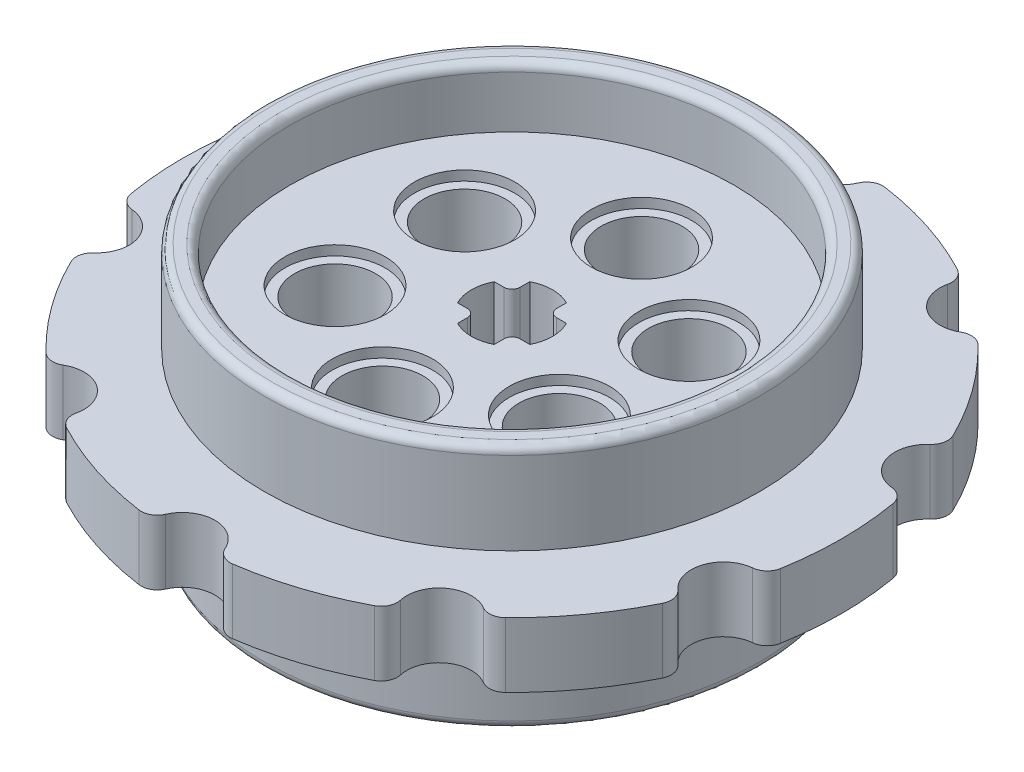
SolidWorks part; units mm, degrees
ref_plane "前视基准面" through (0, 0, 0) normal (0, 0, 1) x (1, 0, 0)
ref_plane "上视基准面" through (0, 0, 0) normal (0, 1, 0) x (1, 0, 0)
ref_plane "右视基准面" through (0, 0, 0) normal (1, 0, 0) x (0, 0, -1)
other "Configuration Table"
sketch "草图1" plane through (0, 0, 0) normal (0, 1, 0) x (1, 0, 0)
  circle A0 centre (0, 0) radius 15.3
  circle A1 centre (0, 0) radius 20.35
  circle A2 centre (0, 0) radius 13.7
  circle A3 centre (0, 20.35) radius 2
  dimension "D1" = 30.6
  dimension "D2" = 40.7
  dimension "D3" = 1.6
  dimension "D4" = 4
extrude "凸台-拉伸1" add sketch "草图1" along normal mid plane 15.2 contours A0 | A2
extrude "凸台-拉伸2" add sketch "草图1<3>" along normal mid plane 4 contours A1
sketch "草图1<3>" plane through (0, 0, 0) normal (0, 1, 0) x (1, 0, 0) same geometry as "草图1"
extrude "切除-拉伸1" cut sketch "草图1<4>" against normal through all both and the other way through all contours A3
sketch "草图1<4>" plane through (0, 0, 0) normal (0, 1, 0) x (1, 0, 0) same geometry as "草图1"
fillet "圆角1" radius 1 2 edges at (1.9976, 0, -20.2517) (-1.9976, 0, -20.2517)
pattern_circular "阵列(圆周)1" count 10 over 360 about axis through (0, 2, 0) along (0, -1, 0) of "切除-拉伸1", "圆角1"
fillet "圆角2" radius 0.5 4 edges at (0, -7.6, 13.7) (0, -7.6, 15.3) (0, 7.6, 13.7) (0, 7.6, 15.3)
extrude "凸台-拉伸3" add sketch "草图1<5>" along normal mid plane 7.8 contours A2
sketch "草图1<5>" plane through (0, 0, 0) normal (0, 1, 0) x (1, 0, 0) same geometry as "草图1"
sketch "草图3" plane through (0, 0, 0) normal (0, 1, 0) x (1, 0, 0)
  line L1 (-1.13, -2.23) -> (1.13, -2.23)
  line L2 (-1.13, -2.23) -> (-1.13, 2.23)
  line L3 (-1.13, 2.23) -> (1.13, 2.23)
  line L4 (1.13, -2.23) -> (1.13, 2.23)
  line L5 (-1.13, -2.23) -> (1.13, 2.23) construction
  line L6 (-1.13, 2.23) -> (1.13, -2.23) construction
  line L7 (-2.23, -1.13) -> (2.23, -1.13)
  line L8 (-2.23, -1.13) -> (-2.23, 1.13)
  line L9 (-2.23, 1.13) -> (2.23, 1.13)
  line L10 (2.23, -1.13) -> (2.23, 1.13)
  line L11 (-2.23, -1.13) -> (2.23, 1.13) construction
  line L12 (-2.23, 1.13) -> (2.23, -1.13) construction
  circle A0 centre (0, 8) radius 2.5
  circle A1 centre (0, 8) radius 3.1
  circle A2 centre (0, 0) radius 2.5
  dimension "D2" = 6.2
  dimension "D3" = 5
  dimension "D1" = 8
  dimension "D4" = 1.1
extrude "切除-拉伸2" cut sketch "草图3" against normal through all both and the other way through all contours A1
extrude "凸台-拉伸4" add sketch "草图3<3>" along normal mid plane 6.6 contours A1 A0 region at (-3.0123, 0, -8)
sketch "草图3<3>" plane through (0, 0, 0) normal (0, 1, 0) x (1, 0, 0) same geometry as "草图3"
pattern_circular "阵列(圆周)2" count 6 over 360 about axis through (0, 7.6, 0) along (0, -1, 0) of "切除-拉伸2", "凸台-拉伸4" reverse direction yes
extrude "切除-拉伸3" cut sketch "草图3<4>" against normal through all both and the other way through all contours L8 A2 | L1 A2 | L10 A2 | L3 A2 | L9 L10 L7 L8 | L2 L3 L4 L1 region at (0, 0, 2.3385) region at (-2.3385, 0, 0) region at (2.3385, 0, 0) region at (0, 0, -2.3385)
sketch "草图3<4>" plane through (0, 0, 0) normal (0, 1, 0) x (1, 0, 0) same geometry as "草图3"
fillet "圆角3" radius 0.5 4 edges at (1.13, 0, 1.13) (1.13, 0, -1.13) (-1.13, 0, -1.13) (-1.13, 0, 1.13)
sketch "草图2" plane through (0, 2, 0) normal (0, 1, 0) x (1, 0, 0)
  line L0 (0, 20.35) -> (11.9614, 16.4635)
  line L1 (-11.9614, 16.4635) -> (0, 20.35)
  arc A0 (-1.834, 19.5523) -> (1.834, 19.5523) centre (0, 20.35) ccw construction
  arc A1 (10.0088, 16.8962) -> (12.9763, 14.7401) centre (11.9614, 16.4635) ccw construction
  arc A2 (-12.9763, 14.7401) -> (-10.0088, 16.8962) centre (-11.9614, 16.4635) ccw construction
  dimension "D1" = 12.577
  dimension "D2" = 12.577
